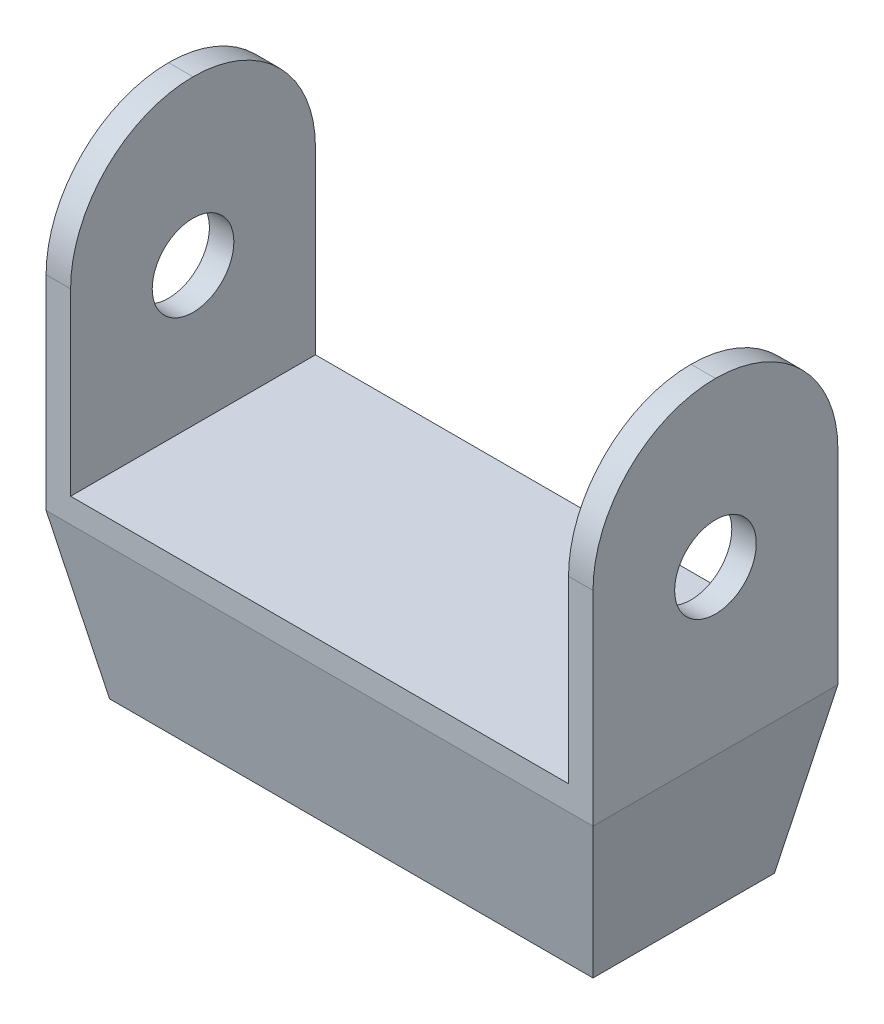
SolidWorks part; units mm, degrees
ref_plane "Front Plane" through (0, 0, 0) normal (0, 0, 1) x (1, 0, 0)
ref_plane "Top Plane" through (0, 0, 0) normal (0, 1, 0) x (1, 0, 0)
ref_plane "Right Plane" through (0, 0, 0) normal (1, 0, 0) x (0, 0, -1)
sketch "Sketch1" plane through (0, 0, 0) normal (0, 0, 1) x (1, 0, 0)
  line L0 (0, 0) -> (30.5, 0)
  line L1 (30.5, 0) -> (30.5, 37)
  line L2 (30.5, 37) -> (33.5, 37)
  line L3 (33.5, 37) -> (33.5, -3)
  line L4 (33.5, -3) -> (0, -3)
  line L5 (0, -3) -> (0, 0)
  dimension "D1" = 30.5
  dimension "D2" = 3
  dimension "D3" = 3
  dimension "D4" = 40
extrude "Boss-Extrude1" add sketch "Sketch1" along normal blind 30
mirror "Mirror1" about plane through (0, -3, 30) normal (1, 0, 0) of "Boss-Extrude1"
sketch "Sketch2" plane through (-33.5, 0, 0) normal (-1, 0, 0) x (0, 0, 1)
  line L0 (30, -3) -> (30, 37) construction
  line L1 (30, 37) -> (0, 37) construction
  circle A0 centre (15, 17) radius 5
  point P4 (30, 17)
  point P7 (15, 37)
  dimension "D1" = 10
extrude "Cut-Extrude1" cut sketch "Sketch2" against normal blind 90
fillet "Fillet1" radius 15 4 edges at (-32, 37, 30) (-32, 37, 0) (32, 37, 0) (32, 37, 30)
sketch "Sketch3" plane through (0, -3, 0) normal (0, -1, 0) x (1, 0, 0)
  line L4 (-33.5, 0) -> (33.5, 0)
  line L5 (33.5, 0) -> (33.5, 30)
  line L6 (33.5, 30) -> (-33.5, 30)
  line L7 (-33.5, 30) -> (-33.5, 0)
  line L8 (-33.5, 0) -> (33.5, 0)
  line L9 (33.5, 0) -> (33.5, 30)
  line L10 (33.5, 30) -> (-33.5, 30)
  line L11 (-33.5, 30) -> (-33.5, 0)
  dimension "D1" = 0
extrude "Boss-Extrude2" add sketch "Sketch3" along normal blind 20 draft 11
sketch "Sketch4" plane through (0, -23, 0) normal (0, -1, 0) x (1, 0, 0)
  line L0 (29.6124, 26.1124) -> (-29.6124, 26.1124) construction
  line L1 (29.6124, 3.8876) -> (29.6124, 26.1124) construction
  circle A0 centre (0, 15) radius 5
  point P5 (0, 26.1124)
  point P9 (29.6124, 15)
  dimension "D1" = 10
extrude "Cut-Extrude2" cut sketch "Sketch4" against normal blind 5
sketch "Sketch5" plane through (0, 0, 0) normal (1, 0, 0) x (0, 0, -1)
  line L0 (-135, 17) -> (-15, 17) construction
  line L1 (-15, 17) -> (-15, 137) construction
  text T0 "X4" font "Century Gothic" height 20
  text T1 "Y4" font "Century Gothic" height 20
  dimension "D1" = 120
ref_plane "Plane1" through (0, 0, 15) normal (0, 0, -1) x (-1, 0, 0)
sketch "Sketch6" plane through (0, 0, 15) normal (0, 0, -1) x (-1, 0, 0)
  line L0 (0, 17) -> (100.3425, 17) construction
  text T0 "Z4" font "Century Gothic" height 20
